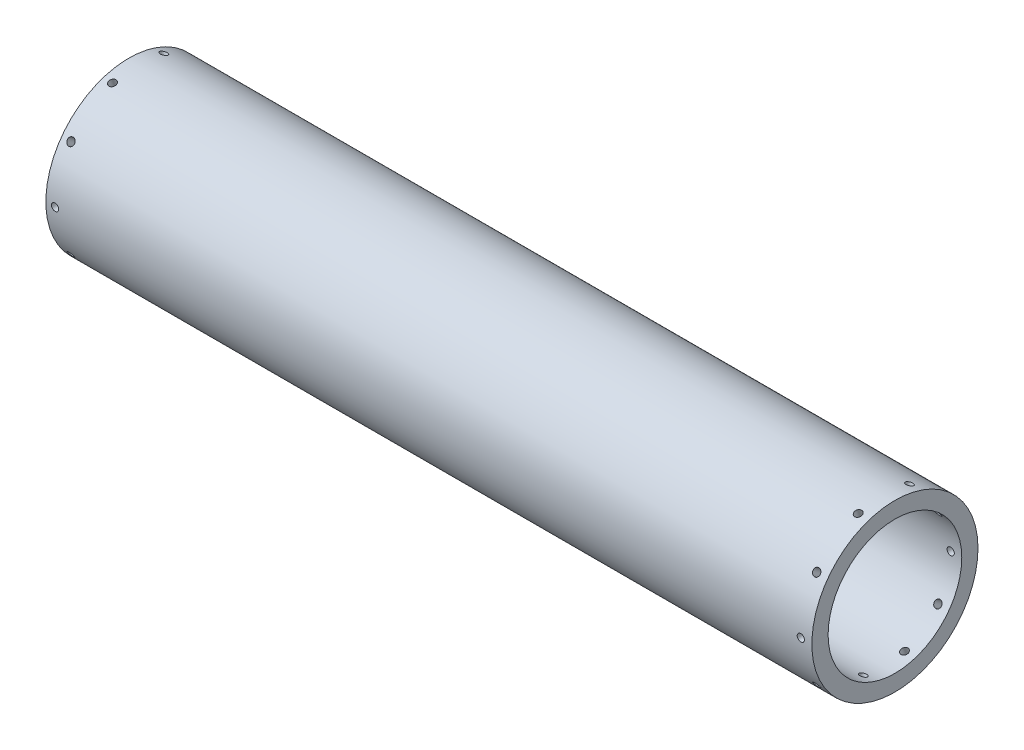
SolidWorks part; units mm, degrees
material "7075-T6 (SN)"
ref_plane "Front Plane" through (0, 0, 0) normal (0, 0, 1) x (1, 0, 0)
ref_plane "Top Plane" through (0, 0, 0) normal (0, 1, 0) x (1, 0, 0)
ref_plane "Right Plane" through (0, 0, 0) normal (1, 0, 0) x (0, 0, -1)
sketch "Sketch1" plane through (0, 0, 0) normal (1, 0, 0) x (0, 0, -1)
  circle A0 centre (0, 0) radius 45.974
  circle A1 centre (0, 0) radius 57.15
  dimension "D1" = 91.948
  dimension "D2" = 114.3
extrude "Boss-Extrude1" add sketch "Sketch1" along normal blind 527.05
sketch "Sketch2" plane through (0, 0, 0) normal (-1, 0, 0) x (0, 0, 1)
  circle A0 centre (0, 0) radius 44.577
  circle A1 centre (0, 0) radius 57.15
  dimension "D1" = 89.154
extrude "Boss-Extrude2" add sketch "Sketch2" against normal blind 88.9
sketch "Sketch3" plane through (0, 0, 0) normal (0, 1, 0) x (1, 0, 0)
  line L0 (0, 0) -> (0, 134.5008) construction
  line L1 (0, 0) -> (634.1169, 0) construction
ref_plane "Plane1" through (0, 0, 57.15) normal (0, 0, 1) x (1, 0, 0)
sketch "Sketch4" plane through (0, 0, 57.15) normal (0, 0, 1) x (1, 0, 0)
  line L0 (527.05, 57.15) -> (527.05, -57.15) construction
  line L1 (527.05, 0) -> (458.7996, 0) construction
  circle A0 centre (519.43, 0) radius 2.4892
  dimension "D1" = 4.9784
  dimension "D2" = 7.62
extrude "Cut-Extrude1" cut sketch "Sketch4" against normal blind 16.51
pattern_circular "CirPattern1" count 10 every 36 about axis through (0, 0, 0) along (1, 0, 0) of "Cut-Extrude1" reverse direction yes
sketch "Sketch5" plane through (0, 0, 57.15) normal (0, 0, 1) x (1, 0, 0)
  line L0 (0, 0) -> (36.2558, 0) construction
  line L1 (0, 57.15) -> (0, -57.15) construction
  circle A0 centre (6.35, 0) radius 2.4892
  dimension "D1" = 4.9784
  dimension "D2" = 6.35
extrude "Cut-Extrude2" cut sketch "Sketch5" against normal blind 17.78
pattern_circular "CirPattern2" count 10 every 36 about axis through (0, 0, 0) along (1, 0, 0) of "Cut-Extrude2"
